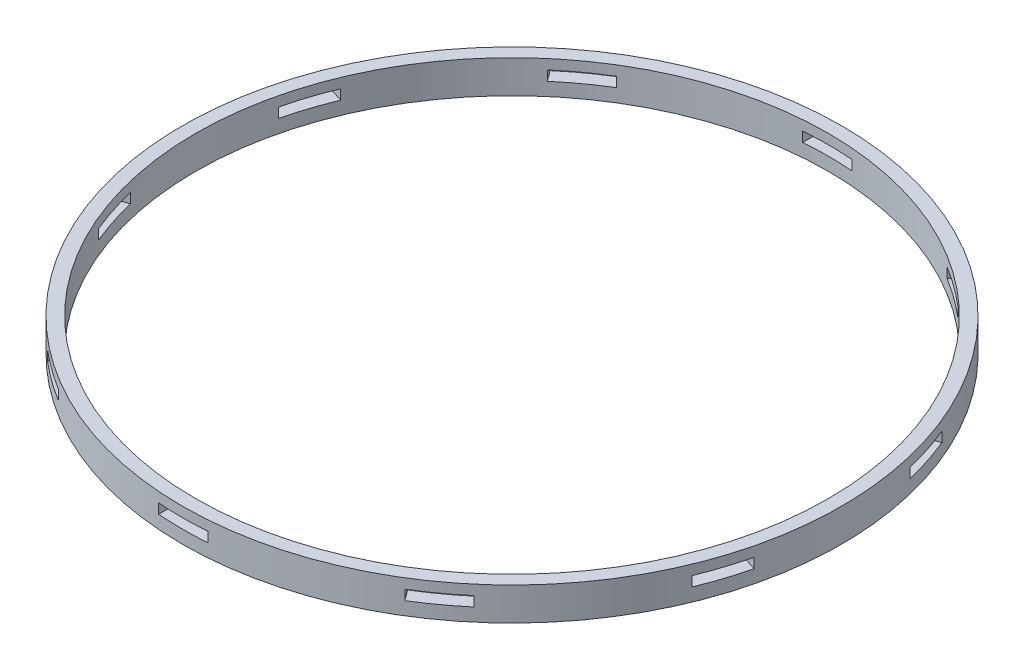
SolidWorks part; units mm, degrees
ref_plane "Front Plane" through (0, 0, 0) normal (0, 0, 1) x (1, 0, 0)
ref_plane "Top Plane" through (0, 0, 0) normal (0, 1, 0) x (1, 0, 0)
ref_plane "Right Plane" through (0, 0, 0) normal (1, 0, 0) x (0, 0, -1)
sketch "Sketch1" plane through (0, 0, 0) normal (0, 1, 0) x (1, 0, 0)
  line L0 (40.8443, 86.8778) -> (42.5461, 90.4977) construction
  circle A0 centre (0, 0) radius 96
  circle A1 centre (0, 0) radius 100
  dimension "D2" = 192
  dimension "D1" = 4
extrude "Boss-Extrude1" add sketch "Sketch1" along normal blind 10
sketch "Sketch2" plane through (0, 0, 0) normal (0, 0, 1) x (1, 0, 0)
  line L0 (-100, 0) -> (100, 0) construction
  line L1 (-7.5, 7) -> (7.5, 7)
  line L2 (-7.5, 7) -> (-7.5, 4)
  line L3 (-7.5, 4) -> (7.5, 4)
  line L4 (7.5, 7) -> (7.5, 4)
  line L5 (96, 10) -> (-96, 10) construction
  point P11 (0, 4)
  dimension "D1" = 4
  dimension "D2" = 3
  dimension "D3" = 15
extrude "Cut-Extrude1" cut sketch "Sketch2" against normal through all
ref_axis "Axis1" through (0, 10, 0) along (0, -1, 0)
pattern_circular "CirPattern1" count 10 over 360 about axis through (0, 10, 0) along (0, -1, 0) of "Cut-Extrude1"
